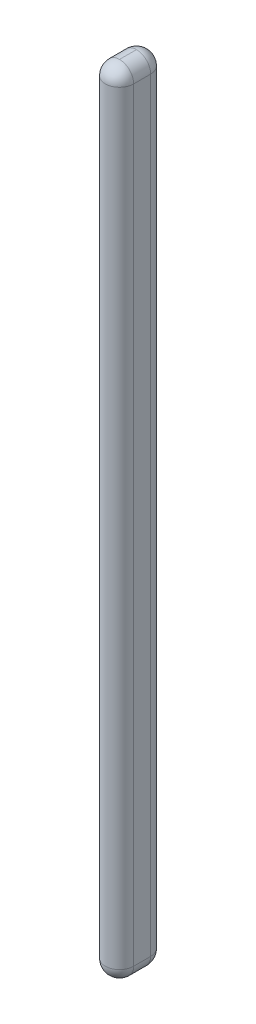
SolidWorks part; units mm, degrees
ref_plane "Front Plane" through (0, 0, 0) normal (1, 0, 0) x (0, 1, 0)
ref_plane "Top Plane" through (0, 0, 0) normal (0, 0, 1) x (0, 1, 0)
ref_plane "Right Plane" through (0, 0, 0) normal (0, 1, 0) x (-1, 0, 0)
sketch "Sketch2" plane through (0, 0, 0) normal (0, 1, 0) x (-1, 0, 0)
  line L0 (0, 7.5) -> (0, -7.5) construction
  line L1 (12.5, 7.5) -> (12.5, -7.5)
  line L2 (-12.5, 7.5) -> (-12.5, -7.5)
  arc A0 (12.5, 7.5) -> (-12.5, 7.5) centre (0, 7.5) ccw
  arc A1 (-12.5, -7.5) -> (12.5, -7.5) centre (0, -7.5) ccw
  point P2 (0, 0)
extrude "Boss-Extrude1" add sketch "Sketch2" along normal mid plane 700
fillet "Fillet1" radius 12.5 8 edges at (12.5, -350, 0) (0, -350, -20) (-12.5, -350, 0) (0, -350, 20) (-12.5, 350, 0) (0, 350, -20) (12.5, 350, 0) (0, 350, 20)
